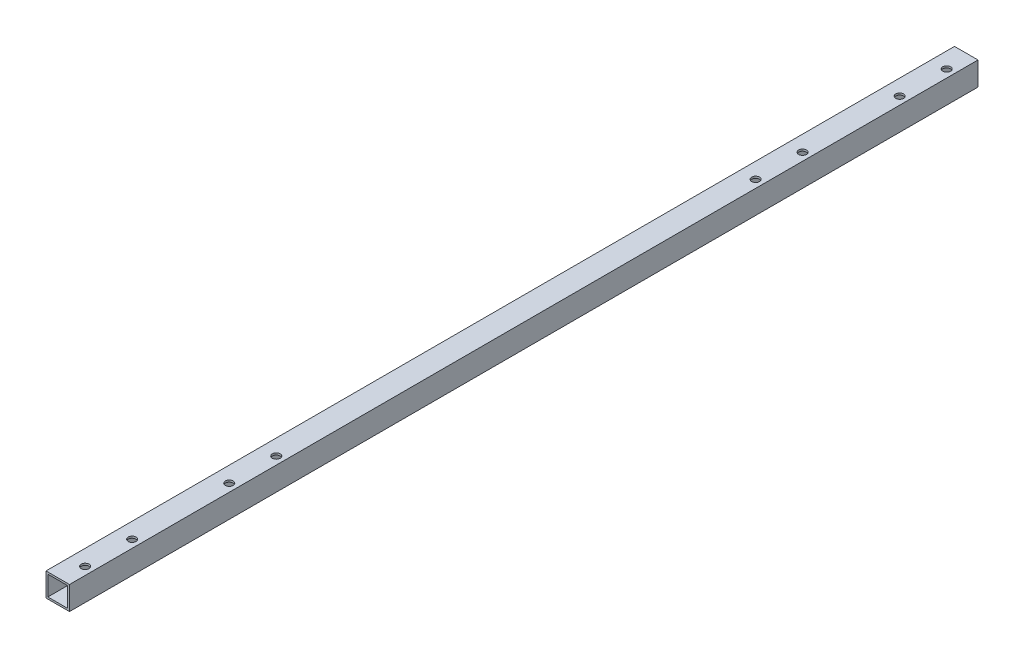
SolidWorks part; units mm, degrees
material "7050-T73510"
ref_plane "Front" through (0, 0, 0) normal (0, 0, 1) x (1, 0, 0)
ref_plane "Top" through (0, 0, 0) normal (0, 1, 0) x (1, 0, 0)
ref_plane "Right" through (0, 0, 0) normal (1, 0, 0) x (0, 0, -1)
sketch "草图1" plane through (0, 0, 0) normal (0, 0, 1) x (1, 0, 0)
  line L0 (-6.3, -6.3) -> (-6.3, 6.3)
  line L1 (-7.5, -7.5) -> (7.5, -7.5)
  line L2 (-7.5, -7.5) -> (-7.5, 7.5)
  line L3 (-7.5, 7.5) -> (7.5, 7.5)
  line L4 (7.5, -7.5) -> (7.5, 7.5)
  line L5 (-7.5, -7.5) -> (7.5, 7.5) construction
  line L6 (-7.5, 7.5) -> (7.5, -7.5) construction
  line L7 (-6.3, 6.3) -> (6.3, 6.3)
  line L8 (6.3, -6.3) -> (6.3, 6.3)
  line L9 (-6.3, -6.3) -> (6.3, -6.3)
  point P0 (0, 0)
  dimension "D1" = 15
  dimension "D2" = 15
  dimension "D3" = 1.2
extrude "凸台-拉伸1" add sketch "草图1" along normal blind 570
sketch "草图2" plane through (0, -7.5, 0) normal (0, -1, 0) x (1, 0, 0)
  circle A12 centre (2.5, 565) radius 2.5
  circle A13 centre (2.5, 535) radius 2.5
  circle A14 centre (2.5, 473) radius 2.5
  circle A15 centre (2.5, 443) radius 2.5
extrude "切除-拉伸1" cut sketch "草图2" against normal blind 25
sketch "草图4" plane through (0, 0, 570) normal (0, 0, 1) x (1, 0, 0)
  line L0 (6.3, 6.3) -> (-6.3, 6.3) construction
  line L1 (6.3, -6.3) -> (6.3, 6.3) construction
  line L2 (-6.3, -6.3) -> (6.3, -6.3) construction
  line L3 (6.3, 6.3) -> (-6.3, 6.3)
  line L4 (7.5, -7.5) -> (7.5, 7.5)
  line L5 (7.5, 7.5) -> (-7.5, 7.5)
  line L6 (-7.5, 7.5) -> (-7.5, -7.5)
  line L7 (-7.5, -7.5) -> (7.5, -7.5)
  line L8 (7.5, -7.5) -> (7.5, 7.5)
  line L9 (7.5, 7.5) -> (-7.5, 7.5)
  line L10 (-7.5, 7.5) -> (-7.5, -7.5)
  line L11 (-7.5, -7.5) -> (7.5, -7.5)
  line L12 (6.3, -6.3) -> (6.3, 6.3)
  line L13 (-6.3, -6.3) -> (6.3, -6.3)
  line M9 (6.3, -6.3) -> (-6.3, -6.3)
  line M10 (-6.3, -6.3) -> (-6.3, 6.3)
  line M11 (-6.3, 6.3) -> (6.3, 6.3)
  line M12 (6.3, 6.3) -> (6.3, -6.3)
  dimension "D1" = 0
extrude "凸台-拉伸2" add sketch "草图4" along normal blind 10 contours M9 M12 M11 M10 | L10 L11 L8 L9 region at (0, 0, 570)
ref_plane "基准面1" through (0, 0, 290) normal (0, 0, 1) x (1, 0, 0)
mirror "镜向1" about plane through (0, 0, 290) normal (0, 0, 1) of "切除-拉伸1"
